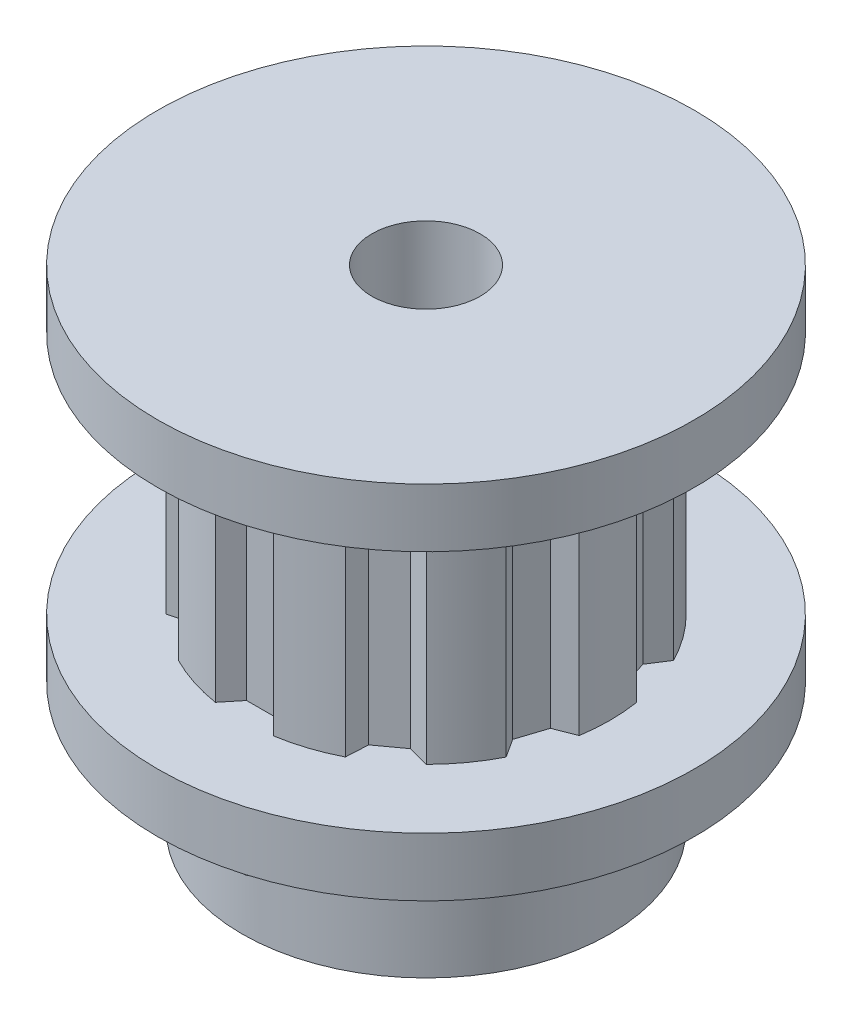
SolidWorks part; units mm, degrees
ref_plane "Front Plane" through (0, 0, 0) normal (0, 0, 1) x (1, 0, 0)
ref_plane "Top Plane" through (0, 0, 0) normal (0, 1, 0) x (1, 0, 0)
ref_plane "Right Plane" through (0, 0, 0) normal (1, 0, 0) x (0, 0, -1)
sketch "Sketch1" plane through (0, 0, 0) normal (0, 1, 0) x (1, 0, 0)
  circle A0 centre (0, 0) radius 11.7983
  circle A1 centre (0, 0) radius 2.3813
extrude "Boss-Extrude1" add sketch "Sketch1" along normal blind 15.875
ref_plane "Midplane" through (0, 7.9375, 0) normal (0, 1, 0) x (-1, 0, 0)
sketch "Sketch4" plane through (0, 7.9375, 0) normal (0, 1, 0) x (-1, 0, 0)
  circle A0 centre (0, 0) radius 8.0899
  circle A1 centre (0, 0) radius 21.0572
extrude "Cut-Extrude2" cut sketch "Sketch4" against normal mid plane 10.7188
sketch "Sketch3" plane through (0, 7.9375, 0) normal (0, 1, 0) x (-1, 0, 0)
  line L0 (-2.3622, 9.3234) -> (2.3622, 9.3234)
  line L1 (2.3622, 9.3234) -> (0.6584, 7.2319)
  line L2 (0.6584, 7.2319) -> (-0.6584, 7.2319)
  line L3 (0, 7.2319) -> (0, 10.9281) construction
  line L4 (-2.3622, 9.3234) -> (-0.6584, 7.2319)
  point P8 (0, 9.3234)
extrude "Cut-Extrude1" cut sketch "Sketch3" against normal mid plane 10.7188
pattern_circular "CirPattern1" count 10 over 360 about axis through (0, 15.875, 0) along (0, 1, 0) of "Cut-Extrude1"
sketch "Sketch6" plane through (0, 0, 0) normal (0, -1, 0) x (1, 0, 0)
  circle A0 centre (0, 0) radius 2.3813
  circle A1 centre (0, 0) radius 8.0899
extrude "Boss-Extrude2" add sketch "Sketch6" along normal blind 5.5562
sketch "Sketch7" plane through (0, 0, 0) normal (0, 0, 1) x (1, 0, 0)
  circle A0 centre (0, -2.4201) radius 0.8255
extrude "Cut-Extrude3" cut sketch "Sketch7" against normal through all and the other way through all
